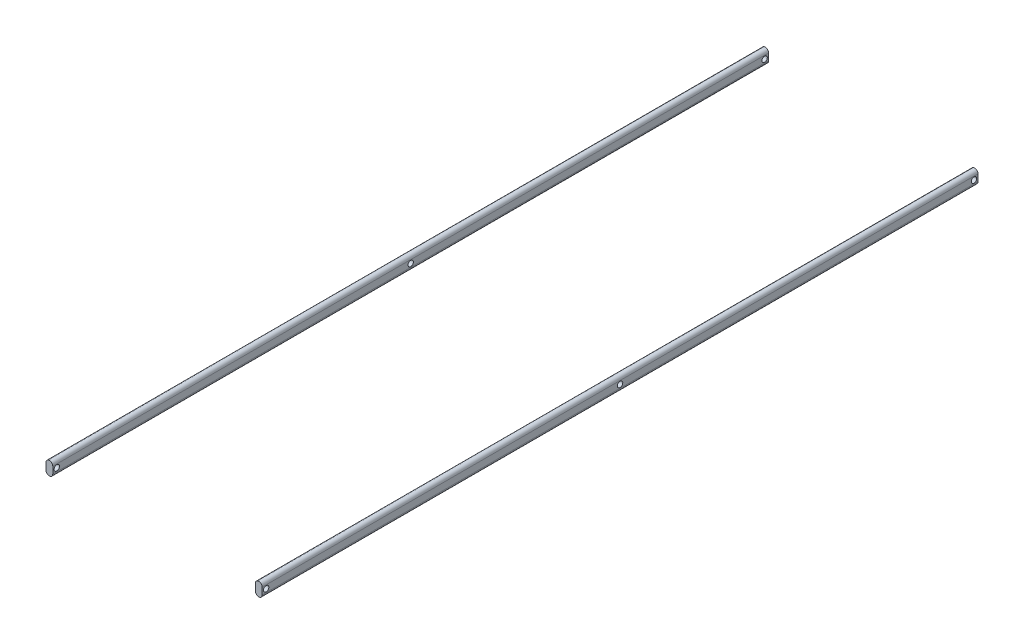
SolidWorks part; units mm, degrees
material "Cast Alloy Steel"
ref_plane "Front Plane" through (0, 0, 0) normal (0, 0, 1) x (1, 0, 0)
ref_plane "Top Plane" through (0, 0, 0) normal (0, 1, 0) x (1, 0, 0)
ref_plane "Right Plane" through (0, 0, 0) normal (1, 0, 0) x (0, 0, -1)
sketch "Sketch1" plane through (0, 0, 0) normal (0, 0, 1) x (1, 0, 0)
  line L0 (-130.6667, 2.75) -> (-130.6667, -7.25)
  line L1 (-130.6667, -7.25) -> (29.3333, -7.25)
  line L2 (29.3333, -7.25) -> (29.3333, 2.75)
  line L3 (29.3333, 2.75) -> (24.3333, 2.75)
  line L4 (24.3333, 2.75) -> (24.3333, -2.25)
  line L5 (24.3333, -2.25) -> (-125.6667, -2.25)
  line L6 (-125.6667, -2.25) -> (-125.6667, 2.75)
  line L7 (-125.6667, 2.75) -> (-130.6667, 2.75)
  dimension "D1" = 5
  dimension "D2" = 5
  dimension "D3" = 5
  dimension "D4" = 5
  dimension "D5" = 5
  dimension "D6" = 160
extrude "Boss-Extrude1" add sketch "Sketch1" along normal blind 530
sketch "Sketch2" plane through (29.3333, 0, 0) normal (1, 0, 0) x (0, 0, -1)
  line L0 (-530, -7.25) -> (-530, 2.75) construction
  line L1 (0, -7.25) -> (0, 2.75) construction
  line L2 (-530, -7.25) -> (0, -7.25) construction
  point P0 (-527, -2.25)
  point P1 (-265, -2.25)
  point P2 (-3, -2.25)
  dimension "D1" = 3
  dimension "D2" = 3
  dimension "D3" = 265
  dimension "D4" = 5
  dimension "D5" = 5
  dimension "D6" = 5
hole_wizard "Ø4.0mm Dowel Hole1" positions "Sketch3" profile "Sketch4" hole size "Ø4.0" standard "ANSI Metric" end condition through all
sketch "Sketch3" plane through (29.3333, 0, 0) normal (1, 0, 0) x (0, 0, -1)
  point P0 (-527, -2.25)
  point P3 (-265, -2.25)
  point P6 (-3, -2.25)
sketch "Sketch4" plane through (29.3333, -2.25, 527) normal (0, 1, 0) x (0, 0, -1)
  line L0 (0, 0) -> (0, 160)
  line L1 (0, 160) -> (2, 160)
  line L2 (2, 160) -> (2, 0)
  line L5 (2, 0) -> (0, 0)
  line L11 (0, -6.35) -> (0, 107.95) construction
  dimension "Thru Hole Dia." = 4
  dimension "Thru Hole Depth" = 160
sketch "Sketch5" plane through (0, -2.25, 0) normal (0, 1, 0) x (1, 0, 0)
  line L0 (24.3333, -795) -> (24.3333, 265) construction
  line L1 (-125.6667, 0) -> (24.3333, 0)
  line L2 (-125.6667, 0) -> (-125.6667, -85.0131)
  line L3 (-125.6667, -85.0131) -> (24.3333, -85.0131)
  line L4 (24.3333, 0) -> (24.3333, -85.0131)
  dimension "D1" = 85.0131
extrude "Cut-Extrude1" cut sketch "Sketch5" against normal blind 10
sketch "Sketch6" plane through (0, -2.25, 0) normal (0, 1, 0) x (1, 0, 0)
  line L0 (24.3333, -263) -> (24.3333, -85.0131) construction
  line L1 (-125.6667, -85.0131) -> (24.3333, -85.0131)
  line L2 (-125.6667, -85.0131) -> (-125.6667, -235.0131)
  line L3 (-125.6667, -235.0131) -> (24.3333, -235.0131)
  line L4 (24.3333, -85.0131) -> (24.3333, -235.0131)
  dimension "D1" = 150
extrude "Cut-Extrude2" cut sketch "Sketch6" against normal through all
sketch "Sketch7" plane through (0, 2.75, 0) normal (0, 1, 0) x (1, 0, 0)
  line L4 (-125.6667, -263) -> (24.3333, -263)
  line L5 (-125.6667, -263) -> (24.3333, -263)
  line L8 (24.3333, -263) -> (24.3333, -235.0131)
  line L9 (24.3333, -235.0131) -> (-125.6667, -235.0131)
  line L10 (-125.6667, -235.0131) -> (-125.6667, -263)
  line L16 (24.3333, -263) -> (24.3333, -235.0131)
  line L17 (24.3333, -235.0131) -> (-125.6667, -235.0131)
  line L18 (-125.6667, -235.0131) -> (-125.6667, -263)
  dimension "D1" = 0
extrude "Boss-Extrude2" add sketch "Sketch7" against normal blind 2
sketch "Sketch8" plane through (0, -7.25, 0) normal (0, -1, 0) x (1, 0, 0)
  line L0 (24.3333, 235.0131) -> (-125.6667, 235.0131)
  line L1 (24.3333, 235.0131) -> (24.3333, 623.6569)
  line L2 (-125.6667, 235.0131) -> (-125.6667, 623.6569)
  line L3 (24.3333, 623.6569) -> (-125.6667, 623.6569)
extrude "Cut-Extrude3" cut sketch "Sketch8" against normal through all
fillet "Fillet1" 2 edges at (29.3333, -7.25, 265) (24.3333, -7.25, 265) type full round first side face at (29.3333, -2.25, 263) second side face at (24.3333, -0.25, 265) middle face at (26.8333, -7.25, 265)
fillet "Fillet2" 2 edges at (29.3333, 2.75, 265) (24.3333, 2.75, 265) type full round first side face at (29.3333, -2.25, 263) second side face at (24.3333, -0.25, 265) middle face at (26.8333, 2.75, 265)
fillet "Fillet3" 2 edges at (-125.6667, -7.25, 265) (-130.6667, -7.25, 265) type full round first side face at (-125.6667, -2.25, 267) second side face at (-130.6667, -2.25, 525) middle face at (-128.1667, -7.25, 265)
fillet "Fillet4" 2 edges at (-130.6667, 2.75, 265) (-125.6667, 2.75, 265) type full round first side face at (-130.6667, -2.25, 525) second side face at (-125.6667, -2.25, 267) middle face at (-128.1667, 2.75, 265)
